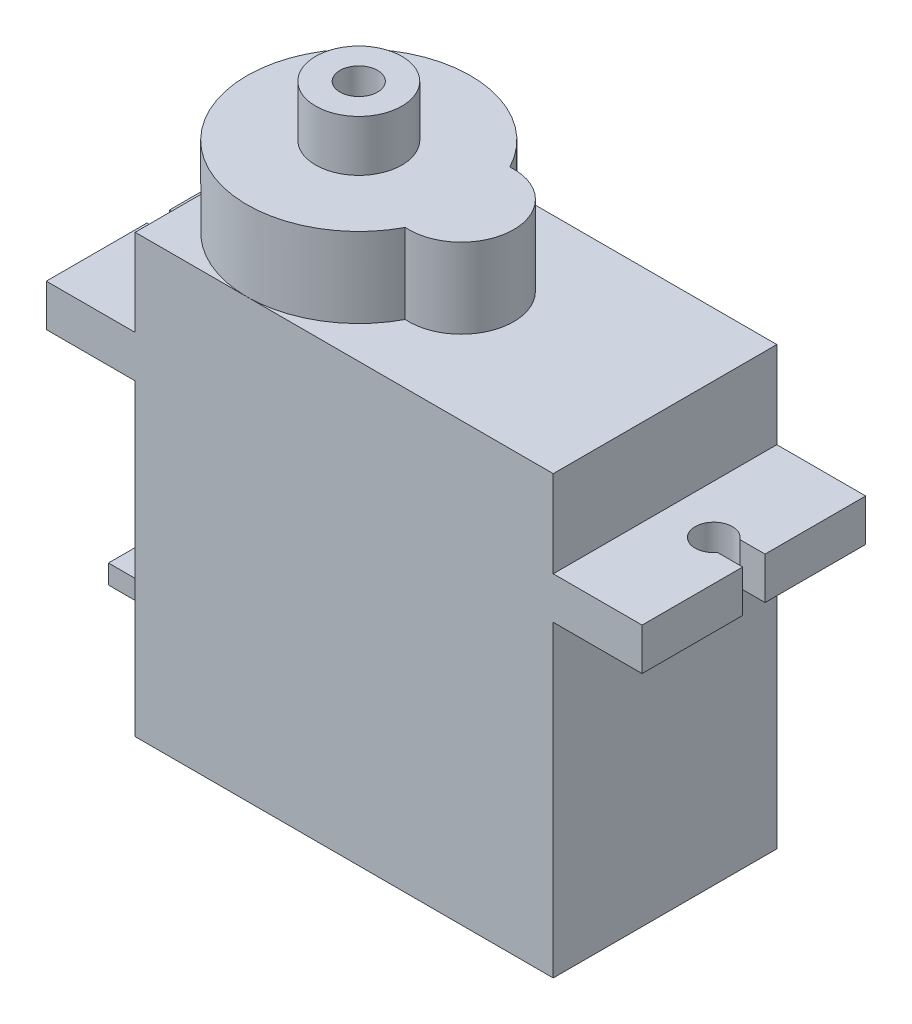
SolidWorks part; units mm, degrees
ref_plane "Front Plane" through (0, 0, 0) normal (0, 0, 1) x (1, 0, 0)
ref_plane "Top Plane" through (0, 0, 0) normal (0, 1, 0) x (1, 0, 0)
ref_plane "Right Plane" through (0, 0, 0) normal (1, 0, 0) x (0, 0, -1)
sketch "Sketch1" plane through (0, 0, 0) normal (0, 1, 0) x (1, 0, 0)
  line L1 (0, 0) -> (22.7711, 0)
  line L2 (0, 0) -> (0, 12.18)
  line L3 (0, 12.18) -> (22.7711, 12.18)
  line L4 (22.7711, 0) -> (22.7711, 12.18)
  dimension "D1" = 12.18
  dimension "D2" = 22.7711
extrude "Boss-Extrude1" add sketch "Sketch1" along normal blind 23.79
ref_plane "Plane1" through (0, 19.0656, 0) normal (0, 1, 0) x (1, 0, 0)
sketch "Sketch3" plane through (0, 19.0656, 0) normal (0, 1, 0) x (1, 0, 0)
  line L0 (22.7711, 12.18) -> (0, 12.18) construction
  line L1 (-4.8387, 0) -> (27.6098, 0)
  line L2 (-4.8387, 0) -> (-4.8387, 12.18)
  line L3 (-4.8387, 12.18) -> (27.6098, 12.18)
  line L4 (27.6098, 0) -> (27.6098, 12.18)
  line L5 (0, 0) -> (22.7711, 0) construction
  point P6 (11.3856, 0)
  point P9 (11.3856, 0)
  dimension "D1" = 32.4485
extrude "Boss-Extrude2" add sketch "Sketch3" against normal blind 2.286
sketch "Sketch4" plane through (0, 19.0656, 0) normal (0, 1, 0) x (1, 0, 0)
  line L0 (-3.4671, 6.6996) -> (-3.4671, 5.4804) construction
  line L1 (-4.8387, 6.6996) -> (-3.4671, 6.6996)
  line L2 (-4.8387, 12.18) -> (-4.8387, 0) construction
  line L3 (-3.4671, 5.4804) -> (-4.8387, 5.4804)
  line L4 (-1.6383, 6.09) -> (-1.6383, 8.3545) construction
  line L5 (11.3856, 12.18) -> (11.3856, 0) construction
  line L6 (22.7711, 12.18) -> (0, 12.18) construction
  line L7 (0, 0) -> (22.7711, 0) construction
  line L8 (24.4094, 6.09) -> (24.4094, 8.3545) construction
  line L9 (26.2382, 6.6996) -> (26.2382, 5.4804) construction
  line L10 (26.2382, 5.4804) -> (27.6098, 5.4804)
  line L11 (27.6098, 6.6996) -> (26.2382, 6.6996)
  line L12 (-4.8387, 6.6996) -> (-4.8387, 5.4804)
  line L13 (27.6098, 6.6996) -> (27.6098, 5.4804)
  arc A0 (-3.4671, 6.6996) -> (-3.4671, 5.4804) centre (-2.6543, 6.09) cw
  arc A1 (26.2382, 6.6996) -> (26.2382, 5.4804) centre (25.4254, 6.09) ccw
  point P6 (-3.4671, 6.09)
  point P8 (-4.8387, 6.09)
  dimension "D1" = 1.016
  dimension "D2" = 3.2004
  dimension "D3" = 1.2192
extrude "Cut-Extrude1" cut sketch "Sketch4" against normal through all
sketch "Sketch5" plane through (0, 23.79, 0) normal (0, 1, 0) x (1, 0, 0)
  line L0 (22.7711, 12.18) -> (0, 12.18) construction
  line L1 (0, 12.18) -> (0, 0) construction
  line L2 (0, 0) -> (22.7711, 0) construction
  line L3 (14.5288, 6.09) -> (14.5288, 9.2952) construction
  arc A0 (11.4717, 8.9405) -> (11.4717, 3.2395) centre (6.09, 6.09) ccw
  arc A1 (11.4717, 3.2395) -> (11.4717, 8.9405) centre (11.6713, 6.09) ccw
  dimension "D1" = 14.5288
  dimension "D2" = 5.715
extrude "Boss-Extrude3" add sketch "Sketch5" along normal blind 4.3434
sketch "Sketch6" plane through (0, 28.1334, 0) normal (0, 1, 0) x (1, 0, 0)
  circle A0 centre (6.09, 6.09) radius 2.3495
  arc A1 (11.4717, 8.9405) -> (11.4717, 3.2395) centre (6.09, 6.09) ccw construction
  dimension "D1" = 4.699
extrude "Boss-Extrude4" add sketch "Sketch6" along normal blind 2.7813 contours A0
sketch "Sketch7" plane through (0, 0, 0) normal (-1, 0, 0) x (0, 0, 1)
  line L0 (-12.18, 0) -> (0, 0) construction
  line L1 (-7.5378, 1.78) -> (-4.6422, 1.78)
  line L2 (-7.5378, 1.78) -> (-7.5378, 2.8214)
  line L3 (-7.5378, 2.8214) -> (-4.6422, 2.8214)
  line L4 (-4.6422, 1.78) -> (-4.6422, 2.8214)
  point P4 (-6.09, 1.78)
  point P7 (-6.09, 0)
  dimension "D1" = 1.0414
  dimension "D2" = 2.8956
  dimension "D3" = 1.78
extrude "Boss-Extrude5" add sketch "Sketch7" along normal blind 6.096
ref_axis "Axis1" through (6.09, 30.9147, -6.09) along (0, -1, 0)
ref_plane "Plane2" through (6.09, 0, 0) normal (-1, 0, 0) x (0, 0, 1)
sketch "Sketch8" plane through (0, 28.1334, 0) normal (0, 1, 0) x (1, 0, 0)
  circle A0 centre (6.09, 6.09) radius 3.556
  dimension "D1" = 7.112
extrude "Boss-Extrude6" [suppressed] add sketch "Sketch8" along normal blind 4.4577
sketch "Sketch9" [suppressed] plane through (0, 31.9532, 0) normal (0, 1, 0) x (1, 0, 0)
  line L0 (2.5019, 6.0579) -> (3.8735, 18.5674)
  line L1 (3.8735, 18.5674) -> (8.2423, 18.5674)
  line L2 (8.2423, 18.5674) -> (9.6139, 6.0579)
  line L3 (6.0579, 6.0579) -> (6.0579, 18.5674) construction
  line L4 (2.5019, 6.0579) -> (9.6139, 6.0579)
  line L5 (8.9281, 12.3127) -> (6.0579, 12.3127) construction
  line L6 (6.0579, 12.3127) -> (3.1877, 12.3127) construction
  circle A0 centre (6.0579, 6.0579) radius 3.556 construction
  point P10 (6.0579, 18.5674)
  point P18 (6.0579, 2.5019)
  dimension "D1" = 4.3688
  dimension "D2" = 16.0655
extrude "Boss-Extrude7" [suppressed] add sketch "Sketch9" against normal blind 1.651
sketch "Sketch11" [suppressed] plane through (0, 31.9532, 0) normal (0, 1, 0) x (1, 0, 0)
  circle A0 centre (6.0579, 6.0579) radius 2.4257
  arc A1 (2.5864, 6.8284) -> (9.5294, 6.8284) centre (6.0579, 6.0579) ccw construction
  dimension "D1" = 4.8514
extrude "Cut-Extrude2" [suppressed] cut sketch "Sketch11" against normal blind 2.54
sketch "Sketch12" [suppressed] plane through (0, 29.4132, 0) normal (0, 1, 0) x (1, 0, 0)
  circle A0 centre (6.0579, 6.0579) radius 1.2001
  dimension "D1" = 2.4003
extrude "Cut-Extrude3" [suppressed] cut sketch "Sketch12" against normal up to surface (1.9177 mm away) up to face at (6.09, 28.1334, -3.7405)
hole_wizard "M2.5x0.45 Tapped Hole1" positions "Sketch14" profile "Sketch15" tap size "M2.5x0.45" standard "ANSI Metric"
sketch "Sketch14" plane through (0, 30.9147, 0) normal (0, 1, 0) x (1, 0, 0)
  point P0 (6.09, 6.09)
sketch "Sketch15" plane through (6.09, 30.9147, -6.09) normal (1, 0, 0) x (0, 0, 1)
  line L0 (0, 0) -> (0, 4.6159)
  line L1 (0, 4.6159) -> (1.025, 4)
  line L2 (1.025, 4) -> (1.025, 0)
  line L5 (1.025, 0) -> (0, 0)
  line L10 (0, 4.6159) -> (-1.025, 4) construction
  line L11 (0, -6.35) -> (0, 107.95) construction
  dimension "Tap Drill Dia." = 2.05
  dimension "Tap Drill Depth" = 4
  dimension "Drill Angle" = 118
cosmetic thread "Hole Thread1" parameters "D1"=4, "D2"=2.5
